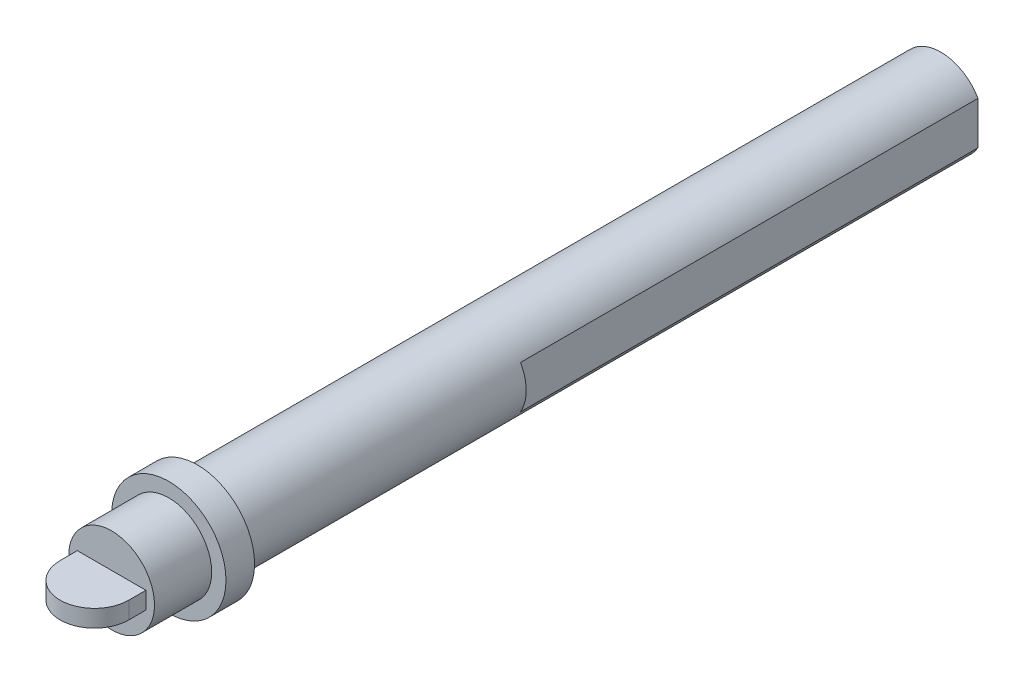
SolidWorks part; units mm, degrees
ref_plane "Front Plane" through (0, 0, 0) normal (0, 0, 1) x (1, 0, 0)
ref_plane "Top Plane" through (0, 0, 0) normal (0, 1, 0) x (1, 0, 0)
ref_plane "Right Plane" through (0, 0, 0) normal (1, 0, 0) x (0, 0, -1)
sketch "Sketch1" plane through (0, 0, 0) normal (0, 0, 1) x (1, 0, 0)
  circle A0 centre (0, 0) radius 10
  dimension "D1" = 20
extrude "Boss-Extrude1" add sketch "Sketch1" along normal blind 5
sketch "Sketch2" plane through (0, 0, 5) normal (0, 0, 1) x (1, 0, 0)
  circle A0 centre (0, 0) radius 7.5
  dimension "D1" = 15
extrude "Boss-Extrude2" add sketch "Sketch2" along normal blind 10 and the other way blind 135
sketch "Sketch3" plane through (0, 0, 15) normal (0, 0, 1) x (1, 0, 0)
  line L1 (6, -1.5) -> (-6, -1.5)
  line L2 (6, -1.5) -> (6, 1.5)
  line L3 (6, 1.5) -> (-6, 1.5)
  line L4 (-6, -1.5) -> (-6, 1.5)
  line L5 (6, -1.5) -> (-6, 1.5) construction
  line L6 (6, 1.5) -> (-6, -1.5) construction
  point P0 (0, 0)
  dimension "D1" = 12
  dimension "D2" = 3
extrude "Boss-Extrude3" add sketch "Sketch3" along normal blind 9
fillet "Fillet1" 2 edges at (-6, 0, 24) (6, 0, 24) type full round first side face at (-6, 0, 19.5) second side face at (6, 0, 19.5) middle face at (0, 0, 24)
sketch "Sketch4" plane through (0, 0, -130) normal (0, 0, -1) x (-1, 0, 0)
  line L0 (-6.5, 6.9849) -> (-6.5, -10.8994)
  line L1 (6.5, 8.8199) -> (6.5, -11.4132)
  line L2 (-6.5, 6.9849) -> (-8.3917, 6.9849)
  line L3 (-8.3917, 6.9849) -> (-8.3917, -10.8994)
  line L4 (-8.3917, -10.8994) -> (-6.5, -10.8994)
  line L5 (6.5, 8.8199) -> (8.0981, 8.8199)
  line L6 (8.0981, 8.8199) -> (8.0981, -11.4132)
  line L7 (8.0981, -11.4132) -> (6.5, -11.4132)
  dimension "D1" = 6.5
  dimension "D2" = 13
extrude "Cut-Extrude1" cut sketch "Sketch4" against normal blind 80
